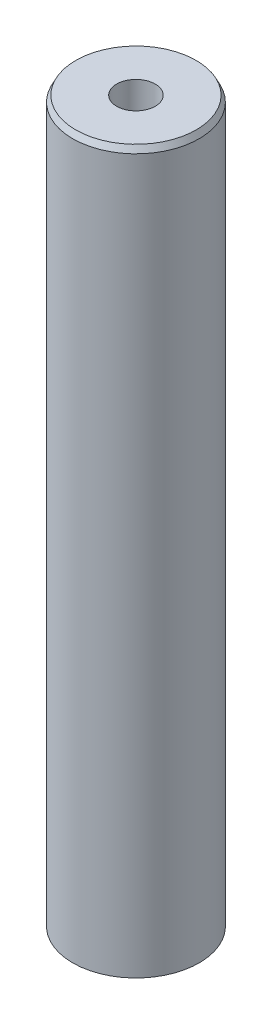
SolidWorks part; units mm, degrees
ref_plane "Front Plane" through (0, 0, 0) normal (0, 0, 1) x (1, 0, 0)
ref_plane "Top Plane" through (0, 0, 0) normal (0, 1, 0) x (1, 0, 0)
ref_plane "Right Plane" through (0, 0, 0) normal (1, 0, 0) x (0, 0, -1)
sketch "Sketch1" plane through (0, 0, 0) normal (0, 1, 0) x (1, 0, 0)
  circle A0 centre (0, 0) radius 52.5
  dimension "SHAFT_OD" = 105
extrude "Boss-Extrude1" add sketch "Sketch1" along normal blind 600
sketch "Sketch2" plane through (0, 0, 0) normal (0, 1, 0) x (1, 0, 0)
  circle A0 centre (0, 0) radius 16.0231
  dimension "BORE_D" = 32.0463
extrude "Cut-Extrude1" cut sketch "Sketch2" along normal through all
chamfer "Chamfer1" distance 5.0635 angle 26.533 2 edges at (0, 600, 52.5) (0, 0, 52.5) first distance on face at (0, 600, 52.5) first distance on face at (0, 0, 16.0231)
